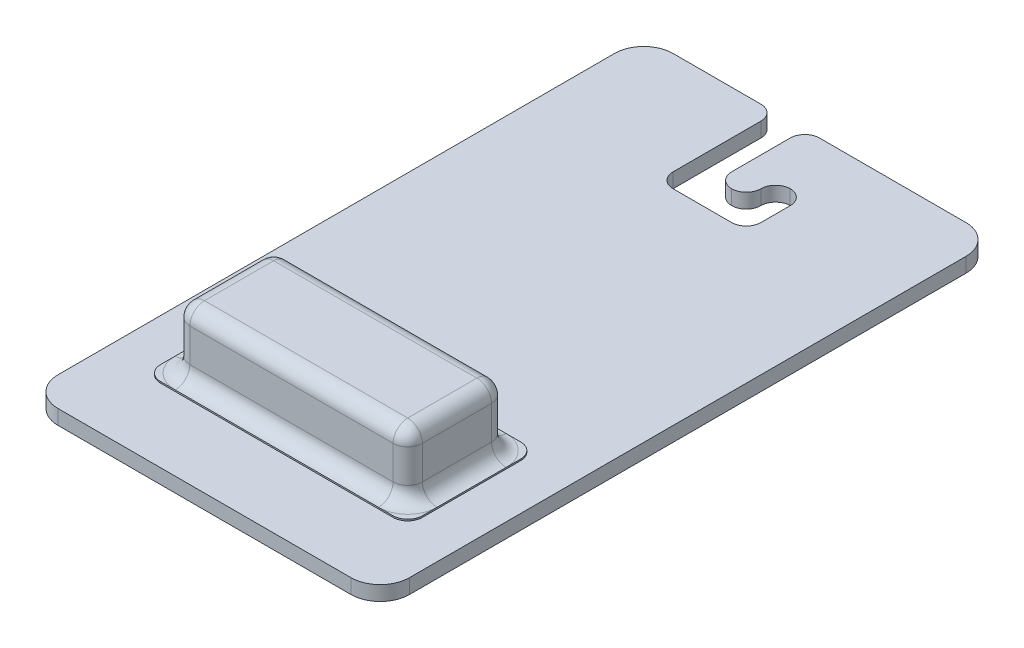
SolidWorks part; units mm, degrees
ref_plane "Front Plane" through (0, 0, 0) normal (0, 0, 1) x (1, 0, 0)
ref_plane "Top Plane" through (0, 0, 0) normal (0, 1, 0) x (1, 0, 0)
ref_plane "Right Plane" through (0, 0, 0) normal (1, 0, 0) x (0, 0, -1)
sketch "Sketch1" plane through (0, 0, 0) normal (0, 1, 0) x (1, 0, 0)
  line L1 (0, 0) -> (7.94, 0)
  line L2 (0, 0) -> (0, 3.36)
  line L3 (0, 3.36) -> (7.94, 3.36)
  line L4 (7.94, 0) -> (7.94, 3.36)
  dimension "D1" = 3.36
  dimension "D2" = 7.94
extrude "Boss-Extrude2" add sketch "Sketch1" along normal blind 2.14
fillet "Fillet1" radius 0.5 4 edges at (3.97, 2.14, -3.36) (7.94, 2.14, -1.68) (3.97, 2.14, 0) (0, 2.14, -1.68)
fillet "Fillet2" radius 0.5 8 edges at (0.1464, 1.9936, -3.2136) (7.7936, 1.9936, -3.2136) (0.1464, 1.9936, -0.1464) (7.94, 0.82, 0) (0, 0.82, -3.36) (7.94, 0.82, -3.36) (0, 0.82, 0) (7.7936, 1.9936, -0.1464)
sketch "Sketch2" plane through (0, 0, 0) normal (0, -1, 0) x (1, 0, 0)
  line L0 (7.94, -0.5) -> (7.94, -2.86) construction
  line L1 (-0.5, 0.5) -> (8.44, 0.5)
  line L2 (-0.5, 0.5) -> (-0.5, -3.86)
  line L3 (-0.5, -3.86) -> (8.44, -3.86)
  line L4 (8.44, 0.5) -> (8.44, -3.86)
  line L5 (-0.5, 0.5) -> (8.44, -3.86) construction
  line L6 (-0.5, -3.86) -> (8.44, 0.5) construction
  line L7 (7.44, -3.36) -> (0.5, -3.36) construction
  line L9 (0.5, 0) -> (7.44, 0) construction
  line L10 (0, -2.86) -> (0, -0.5) construction
  point P0 (3.97, -1.68)
  dimension "D1" = 0.5
  dimension "D2" = 0.5
  dimension "D3" = 0.5
  dimension "D4" = 0.5
extrude "Boss-Extrude3" add sketch "Sketch2" along normal blind 0.05
fillet "Fillet4" radius 0.5 12 edges at (0.1464, 0, -0.1464) (0, 0, -1.68) (0.1464, 0, -3.2136) (3.97, 0, -3.36) (7.7936, 0, -3.2136) (7.94, 0, -1.68) (7.7936, 0, -0.1464) (3.97, 0, 0) (-0.5, -0.025, 0.5) (-0.5, -0.025, -3.86) (8.44, -0.025, -3.86) (8.44, -0.025, 0.5)
shell "Shell1" thickness 0.05 removed face at (3.97, -0.05, -1.68)
sketch "Sketch3" plane through (0, -0.05, 0) normal (0, -1, 0) x (1, 0, 0)
  line L1 (-2, 3) -> (10, 3)
  line L2 (-2, 3) -> (-2, -18)
  line L3 (-2, -18) -> (10, -18)
  line L4 (10, 3) -> (10, -18)
  line L8 (-0.45, -0.1878) -> (-0.45, -3.1722) construction
  point P0 (3.97, -1.68)
  point P15 (-0.45, -1.68)
  dimension "D1" = 3
  dimension "D2" = 12
  dimension "D3" = 10
  dimension "D4" = 18
extrude "Boss-Extrude4" add sketch "Sketch3" along normal blind 0.5
fillet "Fillet5" radius 1 4 edges at (-2, -0.3, 3) (-2, -0.3, -18) (10, -0.3, -18) (10, -0.3, 3)
sketch "Sketch4" plane through (0, -0.05, 0) normal (0, 1, 0) x (1, 0, 0)
  line L0 (2.5, 18) -> (2.5, 14)
  line L1 (-1, 18) -> (9, 18) construction
  line L2 (2.5, 14) -> (5.5, 14)
  line L3 (5.5, 14) -> (5.5, 16)
  line L4 (5.5, 16) -> (4.5, 16)
  line L5 (4.5, 16) -> (4.5, 15)
  line L6 (4.5, 15) -> (3.5, 15)
  line L7 (3.5, 15) -> (3.5, 18)
  point P5 (4, 14)
  point P11 (4, 18)
  dimension "D1" = 1
  dimension "D2" = 1
  dimension "D3" = 2
  dimension "D4" = 1
  dimension "D5" = 3
  dimension "D6" = 4
extrude "Cut-Extrude1" cut sketch "Sketch4" against normal through all and the other way through all
fillet "Fillet6" radius 0.5 6 edges at (3.5, -0.3, -15) (4.5, -0.3, -15) (4.5, -0.3, -16) (5.5, -0.3, -16) (5.5, -0.3, -14) (2.5, -0.3, -14)
fillet "Fillet7" radius 0.5 2 edges at (3.5, -0.3, -18) (2.5, -0.3, -18)
